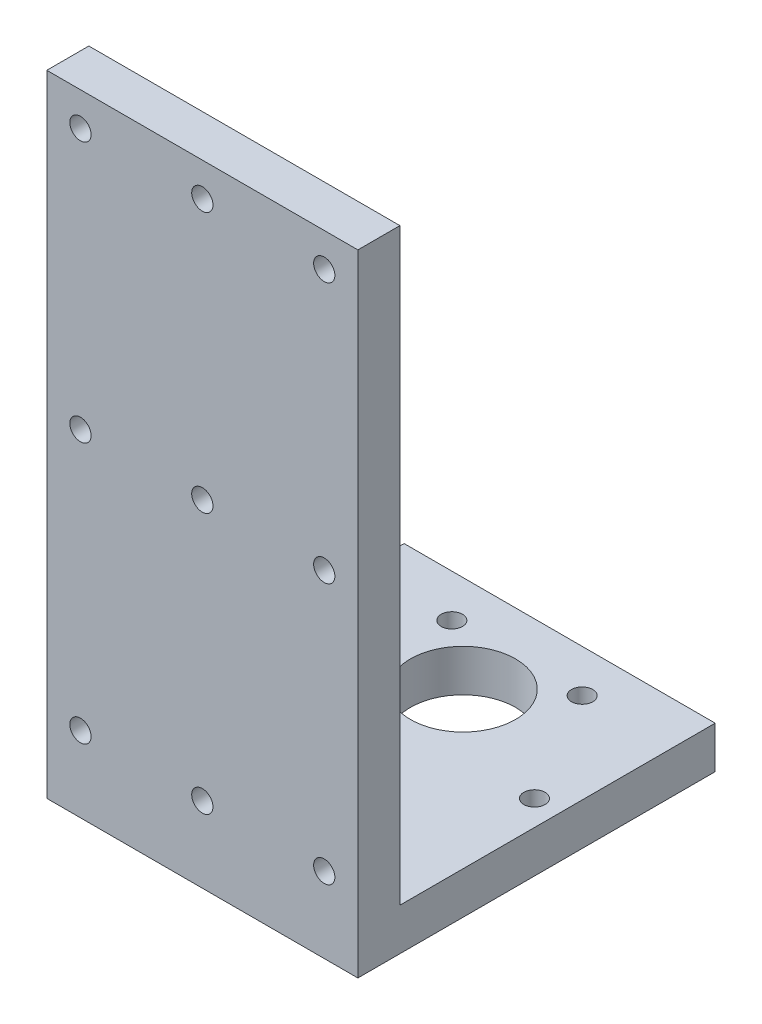
SolidWorks part; units mm, degrees
ref_plane "Plano frontal" through (0, 0, 0) normal (0, 0, 1) x (1, 0, 0)
ref_plane "Plano superior" through (0, 0, 0) normal (0, 1, 0) x (1, 0, 0)
ref_plane "Plano direito" through (0, 0, 0) normal (1, 0, 0) x (0, 0, -1)
sketch "Esboço2" plane through (0, 0, 0) normal (0, 1, 0) x (1, 0, 0)
  line L0 (10.75, 32.4234) -> (18.5, 19) construction
  line L1 (0, 0) -> (37, 0)
  line L2 (0, 0) -> (0, 19)
  line L4 (37, 0) -> (37, 19)
  line L5 (18.5, 19) -> (4.0206, 19) construction
  line L6 (0, 19) -> (0, 37.5)
  line L7 (0, 37.5) -> (37, 37.5)
  line L8 (37, 37.5) -> (37, 19)
  circle A1 centre (10.75, 32.4234) radius 1.265
  circle A2 centre (26.25, 32.4234) radius 1.265
  circle A3 centre (34, 19) radius 1.265
  circle A4 centre (26.25, 5.5766) radius 1.265
  circle A5 centre (10.75, 5.5766) radius 1.265
  circle A6 centre (3, 19) radius 1.265
  point P22 (18.5, 19)
  dimension "D3" = 18.5
  dimension "D4" = 2.53
  dimension "D1" = 37
  dimension "D2" = 19
  dimension "D5" = 15.5
  dimension "D6" = 60
  dimension "D7" = 6
extrude "Ressalto-extrusão1" add sketch "Esboço2" along normal blind 5
sketch "Esboço3" plane through (0, 0, 0) normal (0, -1, 0) x (1, 0, 0)
  line L0 (34, -19) -> (3, -19) construction
  line L1 (18.5, -26) -> (18.5, -19) construction
  circle A0 centre (18.5, -26) radius 6.25
  dimension "D2" = 12.5
  dimension "D1" = 7
extrude "Corte-extrusão1" cut sketch "Esboço3" against normal up to surface (5 mm away) up to face at (18.5, 5, -18.75)
sketch "Esboço4" plane through (0, 0, 0) normal (0, 0, 1) x (1, 0, 0)
  line L1 (0, 0) -> (37, 0)
  line L2 (0, 0) -> (0, 75)
  line L3 (0, 75) -> (37, 75)
  line L4 (37, 0) -> (37, 75)
  circle A0 centre (4, 71) radius 1.265
  circle A1 centre (18.5, 71) radius 1.265
  circle A2 centre (33, 71) radius 1.265
  circle A3 centre (18.5, 40) radius 1.265
  circle A4 centre (33, 40) radius 1.265
  circle A5 centre (18.5, 9) radius 1.265
  circle A6 centre (33, 9) radius 1.265
  circle A7 centre (4, 40) radius 1.265
  circle A8 centre (4, 9) radius 1.265
  dimension "D3" = 2.53
  dimension "D1" = 37
  dimension "D2" = 75
  dimension "D4" = 4
  dimension "D5" = 4
  dimension "D6" = 3
  dimension "D7" = 3
extrude "Ressalto-extrusão2" add sketch "Esboço4" along normal blind 5
